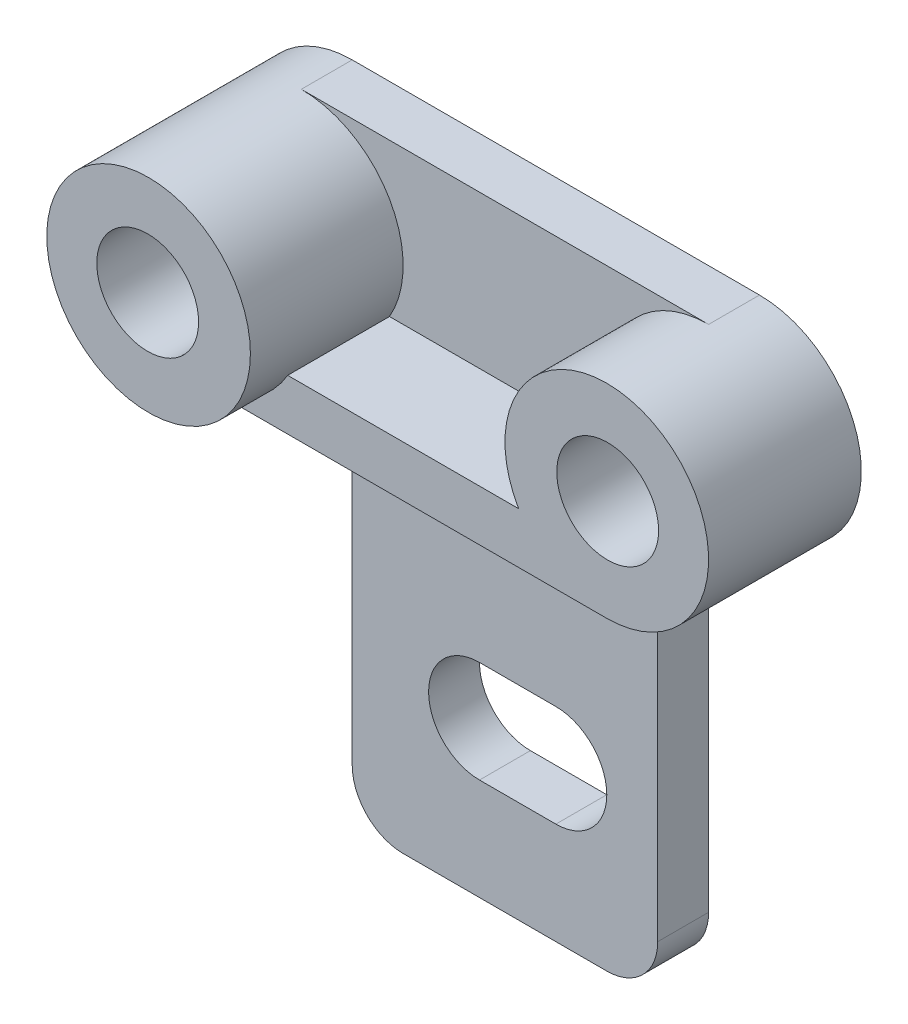
SolidWorks part; units mm, degrees
ref_plane "Front Plane" through (0, 0, 0) normal (0, 0, 1) x (1, 0, 0)
ref_plane "Top Plane" through (0, 0, 0) normal (0, 1, 0) x (1, 0, 0)
ref_plane "Right Plane" through (0, 0, 0) normal (1, 0, 0) x (0, 0, -1)
sketch "Sketch1" plane through (0, 0, 0) normal (0, 0, 1) x (1, 0, 0)
  circle A0 centre (-40, 0) radius 20
  circle A1 centre (40, 0) radius 20
  dimension "D1" = 40
  dimension "D2" = 40
  dimension "D3" = 40
  dimension "D4" = 80
extrude "Boss-Extrude1" add sketch "Sketch1" along normal blind 40 contours A0
extrude "Boss-Extrude2" add sketch "Sketch1<3>" along normal blind 30 separate body contours A1
sketch "Sketch1<3>" plane through (0, 0, 0) normal (0, 0, 1) x (1, 0, 0) same geometry as "Sketch1"
sketch "Sketch2" plane through (0, 0, 0) normal (0, 0, -1) x (-1, 0, 0)
  line L1 (-40, 20) -> (40, 20)
  line L2 (-40, 20) -> (-40, -20)
  line L3 (-40, -20) -> (40, -20)
  line L4 (40, 20) -> (40, -20)
  circle A0 centre (-40, 0) radius 20 construction
  circle A1 centre (40, 0) radius 20 construction
extrude "Boss-Extrude3" add sketch "Sketch2" against normal blind 10
sketch "Sketch3" plane through (0, 0, 30) normal (0, 0, 1) x (1, 0, 0)
  line L0 (40, -20) -> (-40, -20) construction
  line L1 (-40, -10) -> (40, -10)
  line L2 (-40, -10) -> (-40, -20)
  line L3 (-40, -20) -> (40, -20)
  line L4 (40, -10) -> (40, -20)
  circle A1 centre (40, 0) radius 20 construction
  dimension "D1" = 10
extrude "Boss-Extrude4" add sketch "Sketch3" against normal blind 30
hole_wizard "Ø20.0mm Dowel Hole1" positions "Sketch7" profile "Sketch8" hole size "Ø20.0" standard "ISO" end condition through all
sketch "Sketch7" plane through (0, 0, 40) normal (0, 0, 1) x (1, 0, 0)
  point P0 (-40.1782, 0.324)
  point P2 (40.1782, 0)
sketch "Sketch8" plane through (-40.1782, 0.324, 40) normal (1, 0, 0) x (0, -1, 0)
  line L0 (0, 0) -> (0, 40)
  line L1 (0, 40) -> (10, 40)
  line L2 (10, 40) -> (10, 0)
  line L5 (10, 0) -> (0, 0)
  line L11 (0, -6.35) -> (0, 107.95) construction
  dimension "Thru Hole Dia." = 20
  dimension "Thru Hole Depth" = 40
sketch "Sketch9" plane through (0, 0, 0) normal (0, 0, -1) x (-1, 0, 0)
  line L0 (-40, -20) -> (40, -20) construction
  line L1 (-30, -20) -> (30, -20)
  line L2 (-30, -20) -> (-30, -90)
  line L3 (-20, -100) -> (20, -100)
  line L4 (30, -20) -> (30, -90)
  arc A0 (-30, -90) -> (-20, -100) centre (-20, -90) ccw
  arc A1 (20, -100) -> (30, -90) centre (20, -90) ccw
  dimension "D4" = 10
  dimension "D1" = 60
  dimension "D2" = 30
  dimension "D3" = 100
extrude "Boss-Extrude5" add sketch "Sketch9" against normal blind 10
sketch "Sketch10" plane through (0, 0, 10) normal (0, 0, 1) x (1, 0, 0)
  line L0 (-5, -70) -> (10, -70) construction
  line L1 (-5, -60) -> (10, -60)
  line L2 (-5, -80) -> (10, -80)
  line L3 (20, -100) -> (-20, -100) construction
  line L4 (30, -20) -> (30, -90) construction
  arc A0 (-5, -60) -> (-5, -80) centre (-5, -70) ccw
  arc A1 (10, -80) -> (10, -60) centre (10, -70) ccw
  point P2 (2.5, -70)
  dimension "D4" = 10
  dimension "D1" = 30
  dimension "D2" = 20
  dimension "D3" = 15
extrude "Cut-Extrude1" cut sketch "Sketch10" against normal through all
